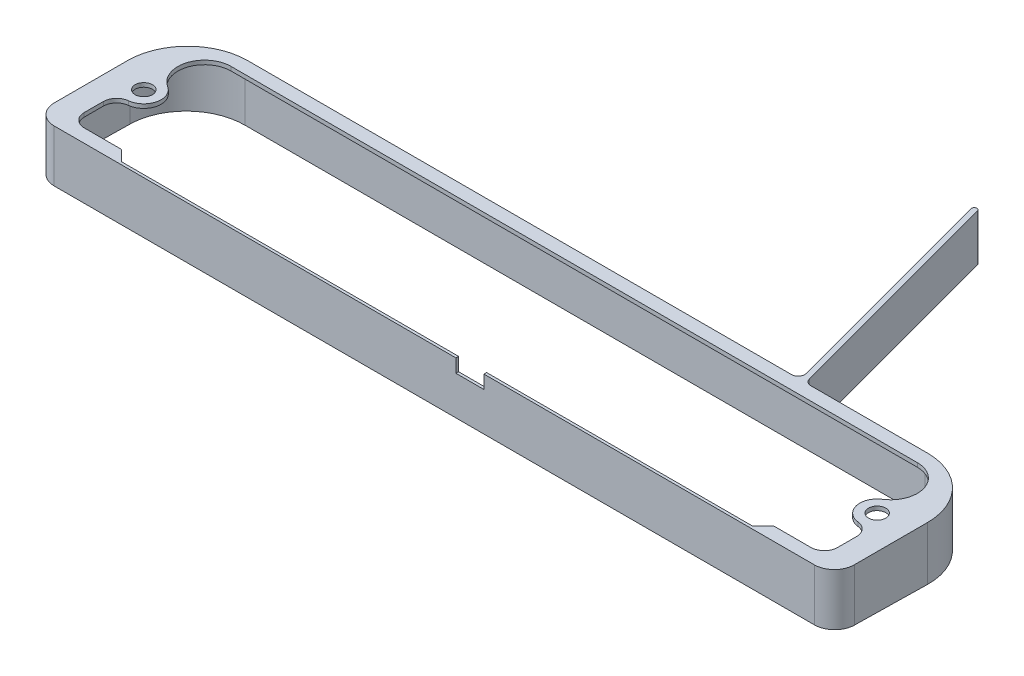
SolidWorks part; units mm, degrees
material "ABS"
ref_plane "Front" through (0, 0, 0) normal (0, 0, 1) x (1, 0, 0)
ref_plane "Top" through (0, 0, 0) normal (0, 1, 0) x (1, 0, 0)
ref_plane "Right" through (0, 0, 0) normal (1, 0, 0) x (0, 0, -1)
ref_axis "X" through (-80.9, 0, 0) along (1, 0, 0)
ref_axis "Y" through (0, -50, 0) along (0, 1, 0)
ref_axis "Z" through (0, 0, -80.9) along (0, 0, 1)
sketch "Sketch1" plane through (0, 0, 0) normal (0, 1, 0) x (1, 0, 0)
  line L0 (-57, 0) -> (-56.5, 0)
  line L2 (-51.4595, 21) -> (51.4595, 21)
  line L4 (56.5, 0) -> (57, 0)
  line L5 (60, 3) -> (60, 14)
  line L6 (51, 23) -> (-51, 23)
  line L7 (-60, 14) -> (-60, 3)
  line L8 (-56.5, 0) -> (56.5, 0)
  line L9 (-49, 0.4) -> (49, 0.4)
  line L10 (-56.5, 0) -> (-56.5, 0.4) construction
  line L11 (56.5, 0) -> (56.5, 0.4) construction
  line L12 (55, 11.43) -> (-55, 11.43) construction
  line L13 (0, 11.43) -> (0, 0) construction
  line L14 (56.5, 2) -> (49, 2)
  line L15 (49, 2) -> (49, 0.4)
  line L16 (-56.5, 2) -> (-49, 2)
  line L17 (-49, 2) -> (-49, 0.4)
  line L18 (-56.5, 0.4) -> (-56.5, 2) construction
  line L19 (-56.5, 0.4) -> (-49, 0.4) construction
  line L20 (56.5, 2) -> (56.5, 0.4) construction
  line L21 (49, 0.4) -> (56.5, 0.4) construction
  line L22 (56.5, 6.8573) -> (56.5, 2)
  line L23 (-56.5, 2) -> (-56.5, 6.8573)
  arc A0 (-53.6053, 13.6242) -> (-51.4595, 21) centre (-51.4595, 17) cw
  arc A1 (51.4595, 21) -> (53.6053, 13.6242) centre (51.4595, 17) cw
  arc A2 (60, 14) -> (51, 23) centre (51, 14) ccw
  arc A3 (-51, 23) -> (-60, 14) centre (-51, 14) ccw
  circle A4 centre (55, 11.43) radius 1.3
  circle A5 centre (-55, 11.43) radius 1.3
  arc A6 (53.6053, 13.6242) -> (54.7174, 8.8454) centre (55, 11.43) ccw
  arc A7 (-53.6053, 13.6242) -> (-54.7174, 8.8454) centre (-55, 11.43) cw
  arc A8 (-54.7174, 8.8454) -> (-56.5, 6.8573) centre (-54.5, 6.8573) ccw
  arc A9 (56.5, 6.8573) -> (54.7174, 8.8454) centre (54.5, 6.8573) ccw
  arc A10 (-57, 0) -> (-60, 3) centre (-57, 3) cw
  arc A11 (60, 3) -> (57, 0) centre (57, 3) cw
  dimension "D5" = 9
  dimension "D6" = 4
  dimension "D10" = 2.6
  dimension "D13" = 2.6
  dimension "D14" = 2
  dimension "D15" = 3
  dimension "D1" = 120
  dimension "D2" = 3.5
  dimension "D3" = 2
  dimension "D4" = 23
  dimension "D7" = 0.4
  dimension "D8" = 11.43
  dimension "D9" = 110
  dimension "D11" = 11
  dimension "D12" = 2
extrude "Boss-Extrude1" add sketch "Sketch1" along normal blind 0.6
sketch "Sketch8" plane through (0, 0, 0) normal (0, -1, 0) x (-1, 0, 0)
  line L4 (51, 22.6) -> (-51, 22.6)
  line L5 (-59.6, 14) -> (-59.6, 3)
  line L12 (-57, 0.4) -> (57, 0.4)
  line L13 (59.6, 3) -> (59.6, 14)
  line L14 (-57, 0) -> (57, 0)
  line L15 (60, 3) -> (60, 14)
  line L16 (51, 23) -> (-51, 23)
  line L17 (-60, 14) -> (-60, 3)
  line L18 (-57, 0) -> (57, 0)
  line L19 (60, 3) -> (60, 14)
  line L20 (51, 23) -> (-51, 23)
  line L21 (-60, 14) -> (-60, 3)
  arc A6 (-51, 22.6) -> (-59.6, 14) centre (-51, 14) ccw
  arc A7 (-59.6, 3) -> (-57, 0.4) centre (-57, 3) ccw
  arc A8 (57, 0.4) -> (59.6, 3) centre (57, 3) ccw
  arc A9 (59.6, 14) -> (51, 22.6) centre (51, 14) ccw
  arc A14 (-60, 3) -> (-57, 0) centre (-57, 3) ccw
  arc A15 (57, 0) -> (60, 3) centre (57, 3) ccw
  arc A16 (60, 14) -> (51, 23) centre (51, 14) ccw
  arc A17 (-51, 23) -> (-60, 14) centre (-51, 14) ccw
  arc A18 (-60, 3) -> (-57, 0) centre (-57, 3) ccw
  arc A19 (57, 0) -> (60, 3) centre (57, 3) ccw
  arc A20 (60, 14) -> (51, 23) centre (51, 14) ccw
  arc A21 (-51, 23) -> (-60, 14) centre (-51, 14) ccw
  dimension "D1" = 0
  dimension "D2" = 0.4
extrude "Boss-Extrude2" add sketch "Sketch8" along normal blind 8.2 from surface starting at face at (0, 0.6, -10.3107)
chamfer "Chamfer1" distance 0.6 angle 45 9 edges at (53, 0, -0.4) (-53, 0, -0.4) (58.8385, 0, -1.1615) (-58.8385, 0, -1.1615) (59.6, 0, -8.5) (-59.6, 0, -8.5) (57.0811, 0, -20.0811) (-57.0811, 0, -20.0811) (0, 0, -22.6)
sketch "Sketch9" plane through (0, 0, 0) normal (1, 0, 0) x (0, 0, -1)
  line L0 (-2, -7.6) -> (23, -7.6)
  line L1 (23, -7.6) -> (-2, -7.1636)
  line L3 (-2, -7.1636) -> (-2, -7.6)
  point P2 (0, 0)
  dimension "D1" = 25
  dimension "D2" = 1
extrude "Cut-Extrude1" cut sketch "Sketch9" against normal through all both and the other way through all
sketch "Sketch11" plane through (0, 0, 0) normal (0, 0, 1) x (1, 0, 0)
  line L0 (3.25, 0.6) -> (3.25, -1.4)
  line L1 (-57, 0.6) -> (57, 0.6) construction
  line L2 (3.25, -1.4) -> (7.45, -1.4)
  line L3 (7.45, -1.4) -> (7.45, 0.6)
  line L4 (7.45, 0.6) -> (3.25, 0.6)
  line L5 (5.35, -1.4) -> (5.35, 0.6) construction
  line L7 (60, 0.6) -> (60, -7.1985) construction
  dimension "D1" = 54.65
  dimension "D2" = 4.2
  dimension "D3" = 2
extrude "Cut-Extrude2" cut sketch "Sketch11" against normal up to next
fillet "Fillet1" radius 2 2 edges at (-56.5, 0.3, -2) (56.5, 0.3, -2)
chamfer "Chamfer2" distance 1.7 angle 45 2 edges at (-49, 0, -0.4) (49, 0, -0.4)
sketch "Sketch12" plane through (0, 0, 0) normal (0, 1, 0) x (1, 0, 0)
  line L1 (-57, 0) -> (57, 0) construction
  line L3 (-70.0161, 72.0463) -> (123.9526, 72.0463) construction
  line L10 (7.45, 0) -> (57, 0) construction
  line L11 (0, 38.0905) -> (0, 0) construction
  line L14 (23.2727, 58.2071) -> (32.7064, 23)
  line L30 (31.8782, 23) -> (22.5, 58)
  line L39 (31.8782, 23) -> (32.7064, 23)
  line L40 (51, 23) -> (-51, 23) construction
  arc A6 (22.5, 58) -> (23.2727, 58.2071) centre (22.8864, 58.1035) cw
  dimension "D3" = 72.0463
  dimension "D1" = 22.5
  dimension "D2" = 35
  dimension "D4" = 15
  dimension "D5" = 0.8
extrude "Boss-Extrude3" add sketch "Sketch12" against normal blind 7 from surface starting at face at (0.7643, 0.6, -7.1934)
fillet "Fillet2" radius 1 2 edges at (31.8782, -2.9, -23) (32.7064, -2.9, -23)
equation "\"D3@Sketch12\"=200-127.95373"
